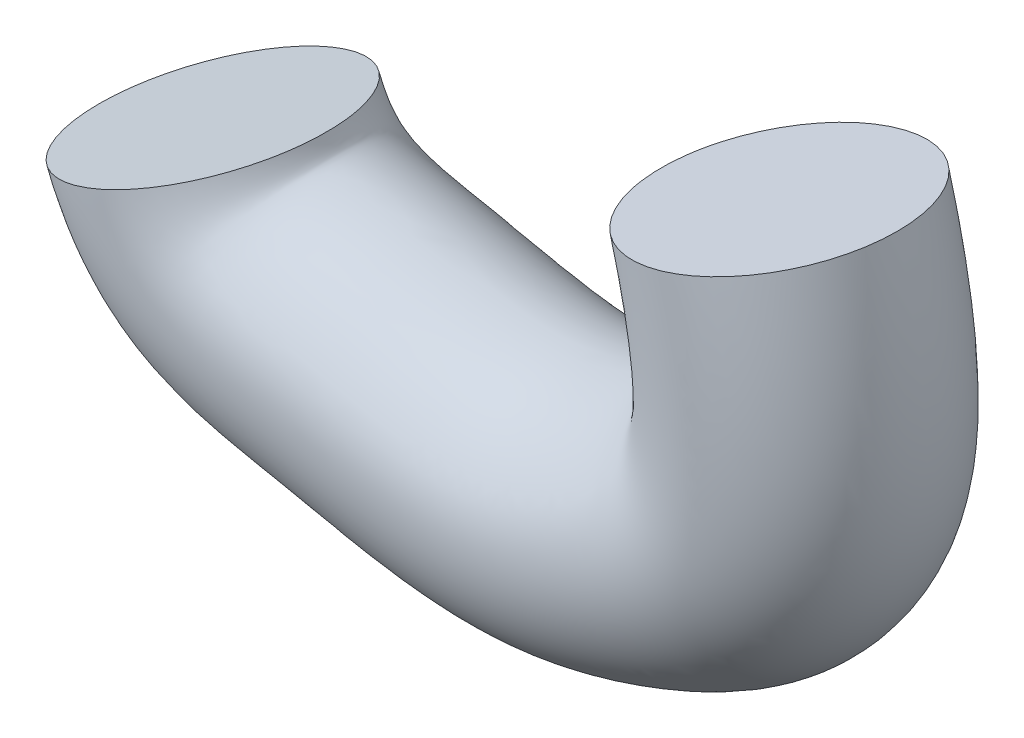
SolidWorks part; units mm, degrees
ref_plane "Front Plane" through (0, 0, 0) normal (0, 0, 1) x (1, 0, 0)
ref_plane "Top Plane" through (0, 0, 0) normal (0, 1, 0) x (1, 0, 0)
ref_plane "Right Plane" through (0, 0, 0) normal (1, 0, 0) x (0, 0, -1)
sketch "Sketch1" plane through (0, 0, 0) normal (0, 0, 1) x (1, 0, 0)
  circle A0 centre (0, 0) radius 20
  spline S0 degree 3 poles (0, 0) (6.3055, -23.6722) (2.2749, -33.8445) (-21.7801, -44.0367) (-31.9064, -43.3667) (-55.2933, -38.1657) (-65.3648, -37.0369) (-69.6407, -26.1277) knots 0 0 0 0 0.319903 0.393283 0.695969 0.760424 1 1 1 1
  point P4 (-69.6407, -26.1277)
sweep "Sweep1" add path "Sketch1" circular profile diameter 30 parameters "D3"=30
